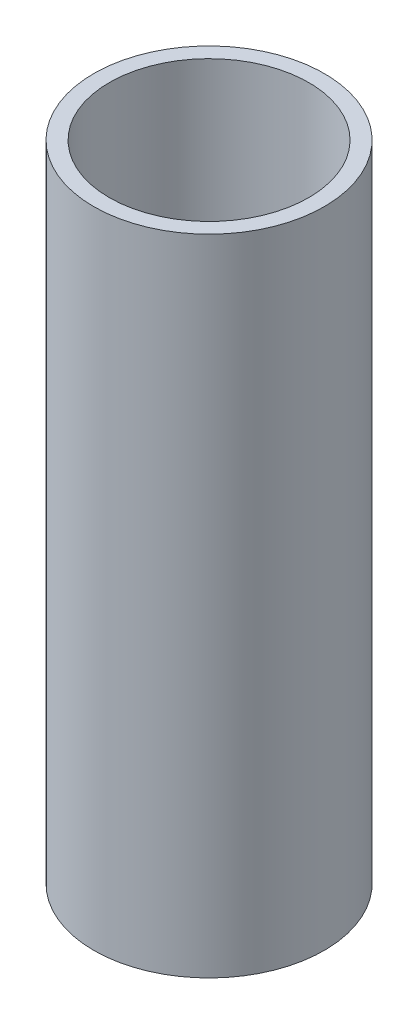
SolidWorks part; units mm, degrees
ref_plane "Front Plane" through (0, 0, 0) normal (0, 0, 1) x (1, 0, 0)
ref_plane "Top Plane" through (0, 0, 0) normal (0, 1, 0) x (1, 0, 0)
ref_plane "Right Plane" through (0, 0, 0) normal (1, 0, 0) x (0, 0, -1)
sketch "Sketch1" plane through (0, 0, 0) normal (0, 1, 0) x (1, 0, 0)
  circle A0 centre (0, 0) radius 30
  dimension "SLEEVE_OD" = 60
extrude "Boss-Extrude1" add sketch "Sketch1" along normal blind 167.6118
sketch "Sketch2" plane through (0, 0, 0) normal (0, 1, 0) x (1, 0, 0)
  circle A0 centre (0, 0) radius 25.9484
  dimension "BORE_D" = 51.8968
extrude "Cut-Extrude1" cut sketch "Sketch2" along normal through all
chamfer "Chamfer1" distance 1.9348 angle 69.801 rebuild error yes
